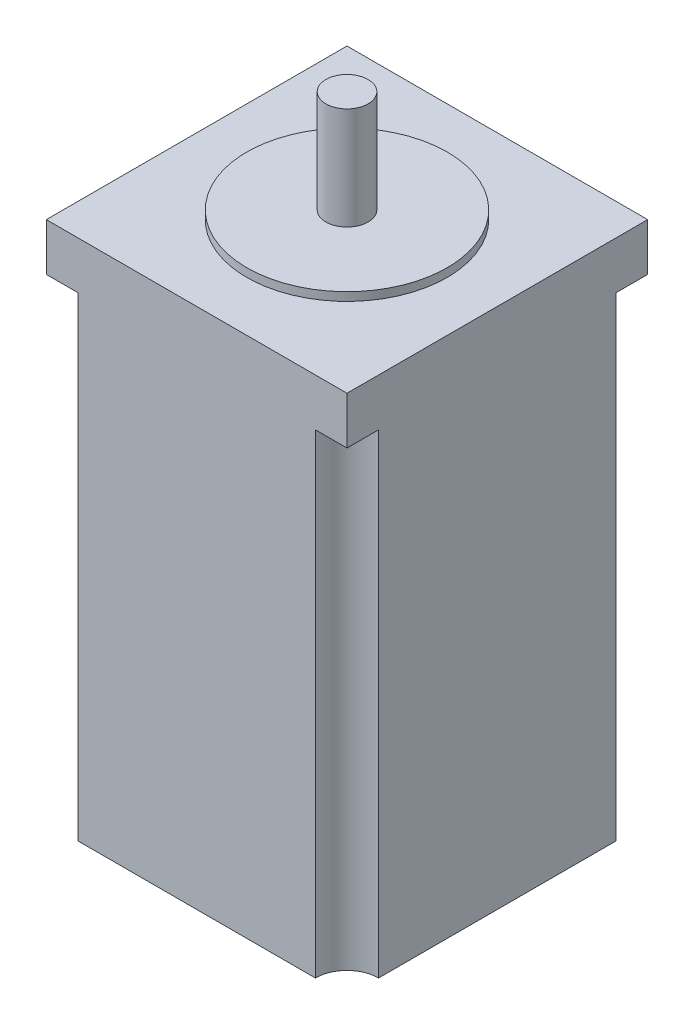
SolidWorks part; units mm, degrees
ref_plane "前视基准面" through (0, 0, 0) normal (0, 0, 1) x (1, 0, 0)
ref_plane "上视基准面" through (0, 0, 0) normal (0, 1, 0) x (1, 0, 0)
ref_plane "右视基准面" through (0, 0, 0) normal (1, 0, 0) x (0, 0, -1)
sketch "草图1" plane through (0, 0, 0) normal (0, 1, 0) x (1, 0, 0)
  line L0 (-28.5, -28.5) -> (28.5, -28.5)
  line L1 (-28.5, -28.5) -> (-28.5, 28.5)
  line L2 (28.5, -28.5) -> (28.5, 28.5)
  line L3 (-28.5, 28.5) -> (28.5, 28.5)
  line L4 (-28.5, -28.5) -> (28.5, 28.5) construction
  line L5 (28.5, -28.5) -> (-28.5, 28.5) construction
  point P1 (0, 0)
  dimension "D1" = 57
  dimension "D2" = 57
extrude "凸台-拉伸1" add sketch "草图1" along normal blind 99
sketch "草图2" plane through (0, 0, 0) normal (0, -1, 0) x (1, 0, 0)
  line L0 (28.5, 28.5) -> (-28.5, 28.5)
  line L1 (28.5, 28.5) -> (28.5, -28.5)
  line L2 (-28.5, 28.5) -> (-28.5, -28.5)
  line L3 (28.5, -28.5) -> (-28.5, -28.5)
  line L4 (28.5, 28.5) -> (-28.5, -28.5) construction
  line L5 (-28.5, 28.5) -> (24.2574, -24.2574) construction
  arc A1 (28.5, -22.5) -> (22.5, -28.5) centre (28.5, -28.5) ccw
  point P1 (0, 0)
  line M8 (28.5, -28.5) -> (28.5, 28.5)
extrude "切除-拉伸1" cut sketch "草图2" against normal blind 90 contours A1 L3 M8 region at (25.9535, 0, -25.9535)
sketch "草图3" plane through (0, 99, 0) normal (0, 1, 0) x (1, 0, 0)
  circle A0 centre (0, 0) radius 4
extrude "凸台-拉伸2" add sketch "草图3" along normal blind 21
ref_axis "基准轴1" through (0, 120, 0) along (0, -1, 0)
pattern_circular "阵列(圆周)1" count 4 over 360 about axis through (0, 120, 0) along (0, -1, 0) of "切除-拉伸1"
sketch "草图4" plane through (0, 99, 0) normal (0, 1, 0) x (1, 0, 0)
  line L4 (-34.8, -34.8) -> (34.8, 34.8) construction
  line L5 (34.8, -34.8) -> (-34.8, 34.8) construction
  circle A0 centre (34.8, 34.8) radius 3.25
  circle A1 centre (-34.8, 34.8) radius 3.25
  circle A2 centre (34.8, -34.8) radius 3.25
  circle A3 centre (-34.8, -34.8) radius 3.25
  point P1 (0, 0)
  dimension "D1" = 69.6
  dimension "D2" = 69.6
sketch "草图5" plane through (0, 99, 0) normal (0, 1, 0) x (1, 0, 0)
  circle A0 centre (0, 0) radius 19
extrude "凸台-拉伸3" add sketch "草图5" along normal blind 1.6
